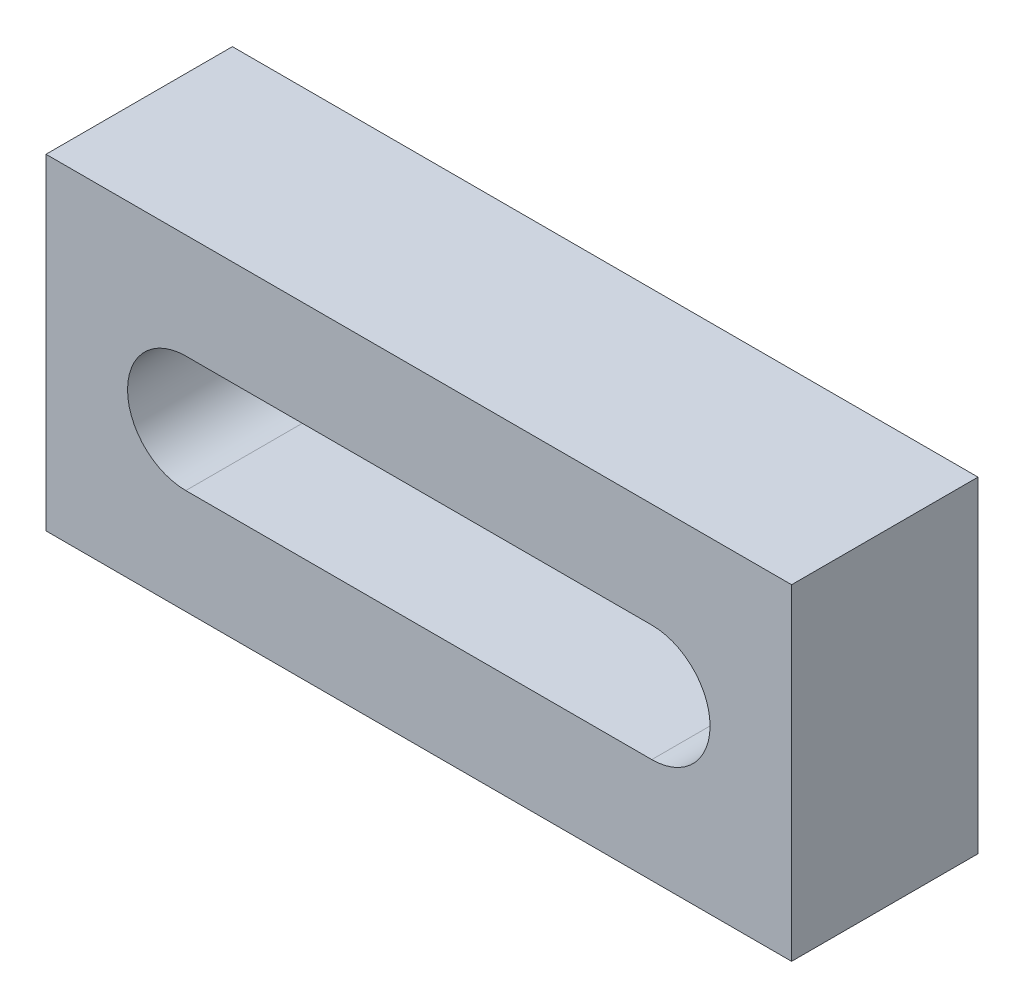
SolidWorks part; units mm, degrees
other "Title Block Table1"
other "DetailItem1"
material "PA Type 6 - Black"
ref_plane "Front Plane" through (0, 0, 0) normal (0, 0, 1) x (1, 0, 0)
ref_plane "Top Plane" through (0, 0, 0) normal (0, 1, 0) x (1, 0, 0)
ref_plane "Right Plane" through (0, 0, 0) normal (1, 0, 0) x (0, 0, -1)
ref_axis "X-Axis" through (-83.7009, 0, 0) along (1, 0, 0)
ref_axis "Y-Axis" through (0, 70.1691, 0) along (0, -1, 0)
ref_axis "Z-Axis" through (0, 0, -88.99) along (0, 0, 1)
sketch "Sketch1" plane through (0, 0, 0) normal (0, 0, 1) x (1, 0, 0)
  line L0 (-25, 0) -> (25, 0) construction
  line L1 (-40, 17.5) -> (40, 17.5)
  line L2 (-40, 17.5) -> (-40, -17.5)
  line L3 (-40, -17.5) -> (40, -17.5)
  line L4 (40, 17.5) -> (40, -17.5)
  line L5 (-40, 17.5) -> (40, -17.5) construction
  line L6 (-40, -17.5) -> (40, 17.5) construction
  line L7 (-25, 6.25) -> (25, 6.25)
  line L8 (-25, -6.25) -> (25, -6.25)
  arc A0 (-25, 6.25) -> (-25, -6.25) centre (-25, 0) ccw
  arc A1 (25, -6.25) -> (25, 6.25) centre (25, 0) ccw
  point P0 (0, 0)
  point P8 (0, 0)
  dimension "D1" = 12.5
  dimension "D2" = 35
  dimension "D3" = 15
  dimension "D4" = 80
extrude "Boss-Extrude1" add sketch "Sketch1" along normal mid plane 20
